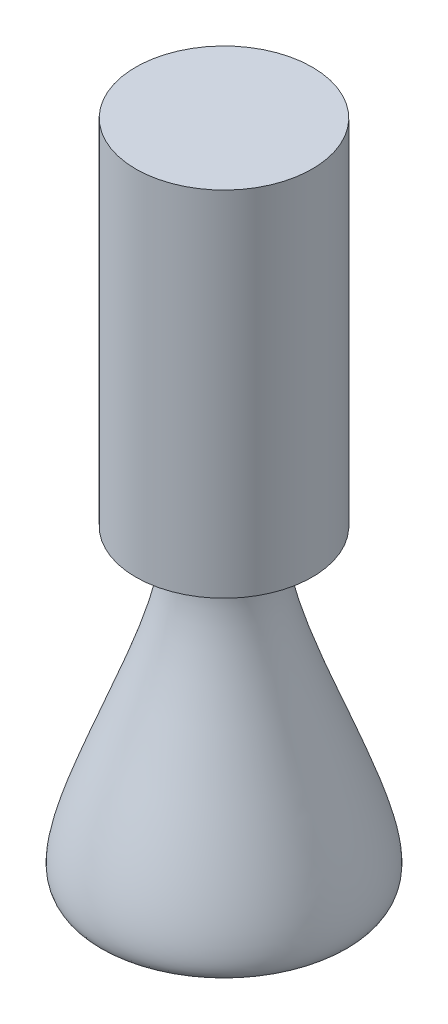
SolidWorks part; units mm, degrees
ref_plane "Front Plane" through (0, 0, 0) normal (0, 0, 1) x (1, 0, 0)
ref_plane "Top Plane" through (0, 0, 0) normal (0, 1, 0) x (1, 0, 0)
ref_plane "Right Plane" through (0, 0, 0) normal (1, 0, 0) x (0, 0, -1)
sketch "Sketch1" plane through (0, 0, 0) normal (0, 0, 1) x (1, 0, 0)
  line L0 (0, 0) -> (17, 0)
  line L1 (12.2351, 42.2158) -> (12.2351, 91.2158)
  line L2 (0, 0) -> (0, 111.9677) construction
  line L3 (12.2351, 91.2158) -> (0, 91.2158)
  line L4 (0, 91.2158) -> (0, 0)
  spline S0 degree 3 poles (17, 0) (21.0678, 5.5861) (-4.6446, 47.4477) (12.2351, 42.2158) knots 0 0 0 0 1 1 1 1
  point P4 (0, 0)
  point P8 (0, 0)
  point P9 (14.4696, 42.3578)
  point P10 (21.1732, 9.6182)
  point P12 (16.967, 9.9687)
  point P13 (15.0392, 12.4223)
  point P14 (12.2351, 42.2158)
  dimension "D2" = 49
  dimension "D1" = 17
  dimension "D3" = 49
revolve "Revolve1" add sketch "Sketch1" angle 360 about L2
